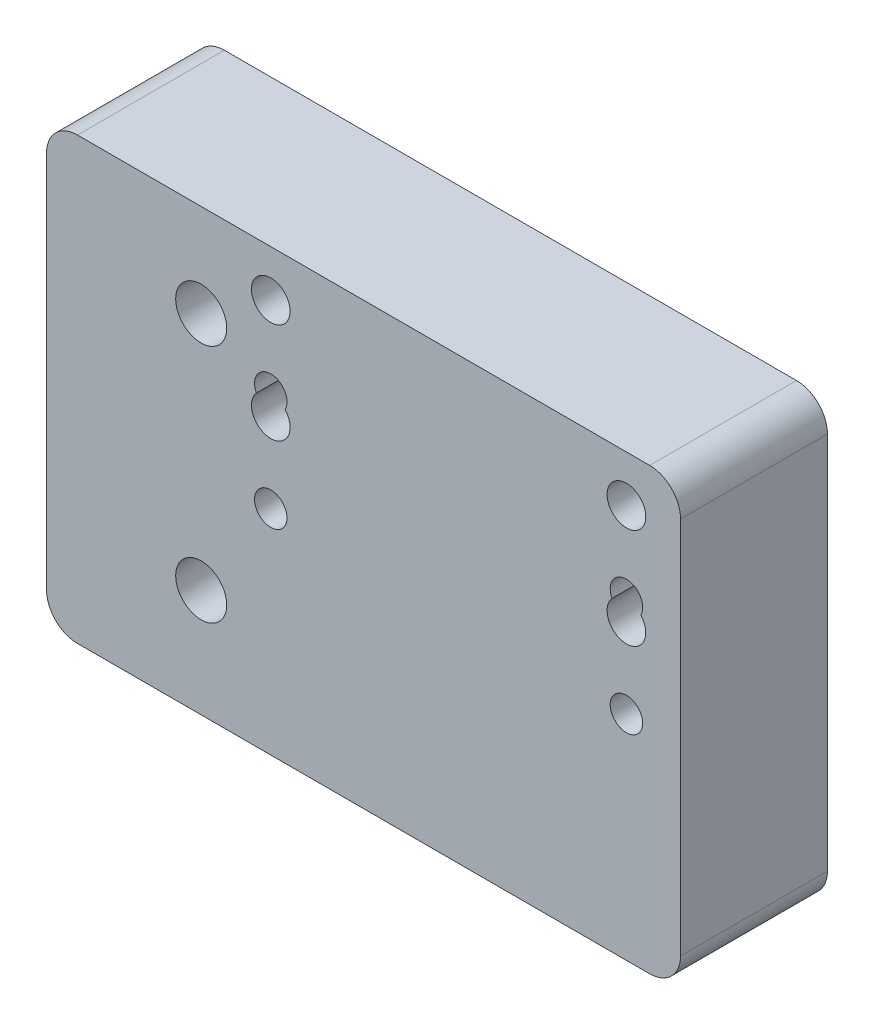
SolidWorks part; units mm, degrees
ref_plane "Front Plane" through (0, 0, 0) normal (0, 0, 1) x (1, 0, 0)
ref_plane "Top Plane" through (0, 0, 0) normal (0, 1, 0) x (1, 0, 0)
ref_plane "Right Plane" through (0, 0, 0) normal (1, 0, 0) x (0, 0, -1)
sketch "Sketch1" plane through (0, 0, 0) normal (0, 0, 1) x (1, 0, 0)
  line L1 (62, 68.7452) -> (-20, 68.7452)
  line L2 (62, 68.7452) -> (62, 8.7452)
  line L3 (62, 8.7452) -> (-20, 8.7452)
  line L4 (-20, 68.7452) -> (-20, 8.7452)
  dimension "D1" = 60
extrude "Boss-Extrude1" add sketch "Sketch1" along normal blind 19
hole_wizard "Tap Drill for M6 Tap1" positions "Sketch4" profile "Sketch3" hole size "M6" standard "ISO" end condition through all
sketch "Sketch4" plane through (0, 0, 19) normal (0, 0, 1) x (1, 0, 0)
  point P0 (9, 58.7452)
  point P3 (55, 58.7452)
  point P6 (55, 58.7452)
  point P9 (9, 58.7452)
  point P13 (55, 45.7452)
  point P15 (9, 45.7452)
sketch "Sketch3" plane through (9, 58.7452, 19) normal (1, 0, 0) x (0, -1, 0)
  line L0 (0, 0) -> (0, 19)
  line L1 (0, 19) -> (2.5, 19)
  line L2 (2.5, 19) -> (2.5, 0)
  line L5 (2.5, 0) -> (0, 0)
  line L11 (0, -6.35) -> (0, 107.95) construction
  dimension "Thru Hole Dia." = 5
  dimension "Thru Hole Depth" = 19
hole_wizard "CSK for M6 Countersunk Flat Head Screw1" positions "Sketch5" profile "Sketch6" countersink size "M6" standard "ISO" end condition through all
sketch "Sketch5" plane through (0, 0, 0) normal (0, 0, 1) x (1, 0, 0)
  line L0 (-20, 8.7452) -> (62, 8.7452) construction
  point P0 (0, 21.7452)
  point P2 (0, 52.7452)
  dimension "D1" = 31
  dimension "D2" = 13
sketch "Sketch6" plane through (0, 21.7452, 0) normal (1, 0, 0) x (0, 1, 0)
  line L0 (0, 0) -> (0, 19)
  line L1 (0, 19) -> (3.3, 19)
  line L2 (3.3, 19) -> (3.3, 3)
  line L3 (3.3, 3) -> (6.3, 0)
  line L5 (6.3, 0) -> (0, 0)
  line L6 (-3.3, 3) -> (-6.3, 0) construction
  line L11 (0, -6.35) -> (0, 107.95) construction
  dimension "Thru Hole Dia." = 6.6
  dimension "Thru Hole Depth" = 19
  dimension "Near C'Sink Dia." = 12.6
  dimension "Near C'Sink Angle" = 90
sketch "Sketch7" plane through (0, 0, 0) normal (0, 0, -1) x (-1, 0, 0)
  line L0 (20, 68.7452) -> (20, 8.7452) construction
  line L1 (20, 68.7452) -> (-62, 68.7452)
  line L2 (20, 68.7452) -> (20, 64.7452)
  line L3 (20, 64.7452) -> (-62, 64.7452)
  line L4 (-62, 68.7452) -> (-62, 64.7452)
  line L5 (-62, 8.7452) -> (-62, 68.7452) construction
extrude "Cut-Extrude1" cut sketch "Sketch7" against normal through all
sketch "Sketch10" plane through (0, 0, 0) normal (0, 0, -1) x (-1, 0, 0)
  line L1 (-62, 8.7452) -> (20, 8.7452)
  line L2 (-62, 8.7452) -> (-62, 7.7952)
  line L3 (-62, 7.7952) -> (20, 7.7952)
  line L4 (20, 8.7452) -> (20, 7.7952)
extrude "Boss-Extrude2" add sketch "Sketch10" against normal blind 19
fillet "Fillet1" radius 4 4 edges at (-20, 7.7952, 9.5) (62, 7.7952, 9.5) (-20, 64.7452, 9.5) (62, 64.7452, 9.5)
hole_wizard "Tap Drill for M5 Tap1" positions "Sketch8" profile "Sketch9" hole size "M5" standard "ISO"
sketch "Sketch8" plane through (0, 7.7952, 0) normal (0, -1, 0) x (-1, 0, 0)
  point P0 (-42, -9.5)
sketch "Sketch9" plane through (42, 7.7952, 9.5) normal (1, 0, 0) x (0, 0, -1)
  line L0 (0, 0) -> (0, 31.2618)
  line L1 (0, 31.2618) -> (2.1, 30)
  line L2 (2.1, 30) -> (2.1, 0)
  line L5 (2.1, 0) -> (0, 0)
  line L10 (0, 31.2618) -> (-2.1, 30) construction
  line L11 (0, -6.35) -> (0, 107.95) construction
  dimension "Hole Dia." = 4.2
  dimension "Hole Depth" = 30
  dimension "Drill Angle" = 118
hole_wizard "Tap Drill for M5 Tap2" positions "Sketch11" profile "Sketch13" hole size "M5" standard "ISO" end condition through all
sketch "Sketch11" plane through (0, 0, 19) normal (0, 0, 1) x (1, 0, 0)
  point P0 (55, 35.3952)
  point P3 (55, 48.3952)
  point P6 (9, 35.3952)
  point P9 (9, 48.3952)
sketch "Sketch13" plane through (55, 35.3952, 19) normal (1, 0, 0) x (0, -1, 0)
  line L0 (0, 0) -> (0, 19)
  line L1 (0, 19) -> (2.1, 19)
  line L2 (2.1, 19) -> (2.1, 0)
  line L5 (2.1, 0) -> (0, 0)
  line L11 (0, -6.35) -> (0, 107.95) construction
  dimension "Thru Hole Dia." = 4.2
  dimension "Thru Hole Depth" = 19
